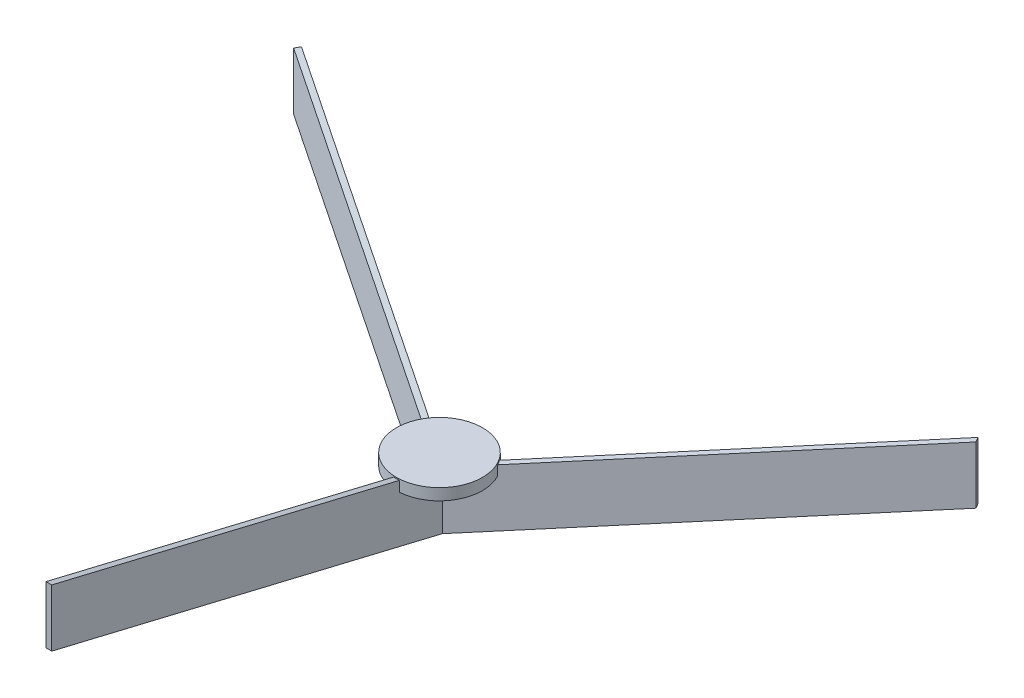
SolidWorks part; units mm, degrees
material "Galvanized Steel"
ref_plane "Front Plane" through (0, 0, 0) normal (0, 0, 1) x (1, 0, 0)
ref_plane "Top Plane" through (0, 0, 0) normal (0, 1, 0) x (1, 0, 0)
ref_plane "Right Plane" through (0, 0, 0) normal (1, 0, 0) x (0, 0, -1)
sketch "Sketch1" plane through (0, 0, 0) normal (0, 1, 0) x (1, 0, 0)
  line L0 (-1.27, 0) -> (0, 2.1997)
  line L1 (0, 2.1997) -> (1.27, 0)
  line L2 (1.27, 0) -> (-1.27, 0)
  dimension "D1" = 2.54
extrude "Boss-Extrude1" add sketch "Sketch1" along normal blind 25.4
sketch "Sketch2" plane through (0, 0, 0) normal (1, 0, 0) x (0, 0, -1)
  line L0 (0, 0) -> (-172.9092, 41.4154)
  line L1 (-172.9092, 41.4154) -> (-172.9092, 66.8154)
  line L2 (-172.9092, 66.8154) -> (0, 25.4)
  line L3 (0, 25.4) -> (0, 0) construction
  line L4 (0, 25.4) -> (0, 0)
  line L5 (-131.9382, 57.002) -> (-131.9382, 46.842) construction
  line L6 (-131.9382, 46.842) -> (-89.5202, 46.842) construction
  dimension "D1" = 177.8
  dimension "D2" = 42.418
  dimension "D3" = 10.16
extrude "Boss-Extrude2" add sketch "Sketch2" against normal mid plane 2.54
ref_point "Point1"
ref_axis "Axis1" through (0, 25.4, -0.7332) along (0, 1, 0)
pattern_circular "CirPattern3" count 3 every 120 about axis through (0, 25.4, -0.7332) along (0, 1, 0) of "Boss-Extrude2"
sketch "Sketch3" plane through (0, 25.4, 0) normal (0, 1, 0) x (1, 0, 0)
  circle A0 centre (0, 0) radius 19.05
  dimension "D1" = 38.1
extrude "Boss-Extrude3" add sketch "Sketch3" along normal blind 5.08
